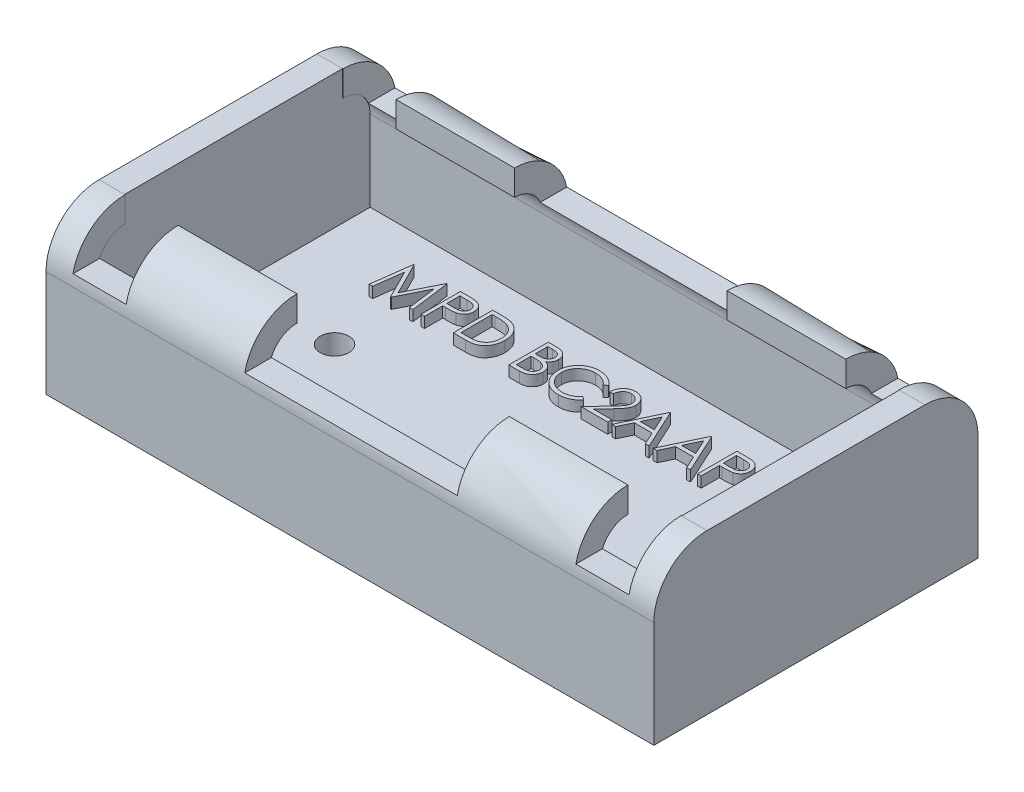
SolidWorks part; units mm, degrees
ref_plane "Front" through (0, 0, 0) normal (0, 0, 1) x (1, 0, 0)
ref_plane "Top" through (0, 0, 0) normal (0, 1, 0) x (1, 0, 0)
ref_plane "Right" through (0, 0, 0) normal (1, 0, 0) x (0, 0, -1)
sketch "Sketch1" plane through (0, 0, 0) normal (0, 1, 0) x (1, 0, 0)
  line L1 (-28.6, 15.25) -> (28.6, 15.25)
  line L2 (-28.6, 15.25) -> (-28.6, -15.25)
  line L3 (-28.6, -15.25) -> (28.6, -15.25)
  line L4 (28.6, 15.25) -> (28.6, -15.25)
  line L5 (-28.6, 15.25) -> (28.6, -15.25) construction
  line L6 (-28.6, -15.25) -> (28.6, 15.25) construction
  point P0 (0, 0)
  dimension "D1" = 57.2
  dimension "D2" = 30.5
extrude "Boss-Extrude1" add sketch "Sketch1" along normal mid plane 15
fillet "Fillet5" radius 5 2 edges at (0, 7.5, -15.25) (0, 7.5, 15.25)
shell "Shell6" thickness 2.4 removed face at (0, 7.5, 0)
sketch "Sketch2" plane through (0, 0, 15.25) normal (0, 0, 1) x (1, 0, 0)
  line L1 (-26.16, 3.5) -> (-21.16, 3.5)
  line L2 (-26.16, 3.5) -> (-26.16, 7.5)
  line L3 (-26.16, 7.5) -> (-21.16, 7.5)
  line L4 (-21.16, 3.5) -> (-21.16, 7.5)
  line L5 (-26.16, 3.5) -> (-21.16, 7.5) construction
  line L6 (-26.16, 7.5) -> (-21.16, 3.5) construction
  line L8 (26.16, 3.5) -> (21.16, 3.5)
  line L9 (26.16, 3.5) -> (26.16, 7.5)
  line L10 (26.16, 7.5) -> (21.16, 7.5)
  line L11 (21.16, 3.5) -> (21.16, 7.5)
  line L12 (26.16, 3.5) -> (21.16, 7.5) construction
  line L13 (26.16, 7.5) -> (21.16, 3.5) construction
  line L14 (10, 3.5) -> (-10, 3.5)
  line L15 (10, 3.5) -> (10, 7.5)
  line L16 (10, 7.5) -> (-10, 7.5)
  line L17 (-10, 3.5) -> (-10, 7.5)
  line L18 (10, 3.5) -> (-10, 7.5) construction
  line L19 (10, 7.5) -> (-10, 3.5) construction
  line L22 (-28.6, 2.5) -> (-28.6, -7.5) construction
  line L23 (28.6, 2.5) -> (28.6, -7.5) construction
  line L24 (-28.6, 7.5) -> (28.6, 7.5) construction
  point P4 (-23.66, 5.5)
  point P11 (23.66, 5.5)
  point P16 (0, 5.5)
  point P21 (0, 0)
  point P22 (0, 0)
  point P23 (0, 0)
  point P29 (-34.8928, 10.9946)
  point P30 (0, 0)
  dimension "D1" = 5
  dimension "D2" = 5
  dimension "D3" = 20
  dimension "D4" = 2.44
  dimension "D5" = 2.44
  dimension "D6" = 4
extrude "Cut-Extrude3" cut sketch "Sketch2" against normal through all
sketch "Sketch3" plane through (0, -5.1, 0) normal (0, 1, 0) x (1, 0, 0)
  line L0 (28.6, -15.25) -> (28.6, 15.25) construction
  circle A0 centre (0, 0) radius 1.78
  circle A1 centre (16, 0) radius 1.35
  circle A2 centre (-16.7, 0) radius 1.35
  point P11 (0, 0)
  dimension "D1" = 2.7
  dimension "D2" = 2.7
  dimension "D5" = 3.56
  dimension "D3" = 32.7
  dimension "D4" = 12.6
extrude "Cut-Extrude4" cut sketch "Sketch3" against normal through all
sketch "Sketch4" plane through (0, -5.1, 0) normal (0, 1, 0) x (1, 0, 0)
  text T0 "+"
extrude "Boss-Extrude2" add sketch "Sketch4" along normal blind 1
sketch "Sketch5" plane through (0, -5.1, 0) normal (0, 1, 0) x (1, 0, 0)
  text T0 "MPD BC2AAPC" font "Century Gothic" height in points 14
extrude "Boss-Extrude3" add sketch "Sketch5" along normal blind 1
equation "\"D5@Sketch2\"=\"D4@Sketch2\""
equation "\"D2@Sketch3\"=\"D1@Sketch3\""
